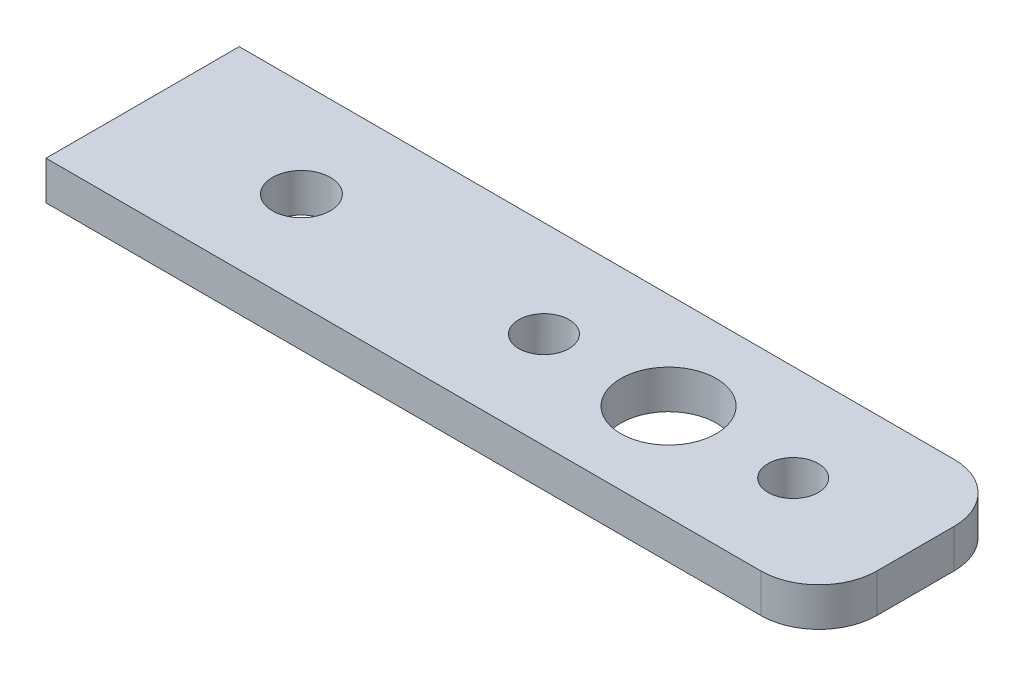
SolidWorks part; units mm, degrees
ref_plane "Front Plane" through (0, 0, 0) normal (0, 0, 1) x (1, 0, 0)
ref_plane "Top Plane" through (0, 0, 0) normal (0, 1, 0) x (1, 0, 0)
ref_plane "Right Plane" through (0, 0, 0) normal (1, 0, 0) x (0, 0, -1)
sketch "Sketch1" plane through (0, 0, 0) normal (0, 1, 0) x (1, 0, 0)
  line L1 (-20, 5) -> (20, 5)
  line L2 (-20, 5) -> (-20, -5)
  line L3 (-20, -5) -> (20, -5)
  line L4 (20, 5) -> (20, -5)
  line L5 (-20, 5) -> (20, -5) construction
  line L6 (-20, -5) -> (20, 5) construction
  point P0 (0, 0)
  dimension "D1" = 10
  dimension "D2" = 40
extrude "Boss-Extrude1" add sketch "Sketch1" along normal blind 2
sketch "Sketch2" plane through (0, 2, 0) normal (0, 1, 0) x (1, 0, 0)
  line L0 (7.2199, 5) -> (7.2199, -5) construction
  line L1 (-20, -5) -> (20, -5) construction
  circle A0 centre (7.2199, 0) radius 2.4729
  circle A1 centre (13.6699, 0) radius 1.3
  circle A3 centre (0.7699, 0) radius 1.3
  point P10 (7.2199, 0)
  point P11 (7.2199, 0)
  dimension "D1" = 2.6
  dimension "D2" = 6.45
extrude "Cut-Extrude1" cut sketch "Sketch2" against normal blind 3
fillet "Fillet1" radius 3 2 edges at (20, 1, 5) (20, 1, -5)
hole_wizard "Ø3.0 (3) Diameter Hole1" positions "Sketch3" profile "Sketch4" hole size "Ø3.0" standard "BSI" end condition through all
sketch "Sketch3" plane through (0, 2, 0) normal (0, 1, 0) x (1, 0, 0)
  point P0 (-11.7813, 0)
  point P3 (-6.9218, 0)
  point P4 (-11.7813, 0)
sketch "Sketch4" plane through (-11.7813, 2, 0) normal (1, 0, 0) x (0, 0, 1)
  line L0 (0, 0) -> (0, 2)
  line L1 (0, 2) -> (1.5, 2)
  line L2 (1.5, 2) -> (1.5, 0)
  line L5 (1.5, 0) -> (0, 0)
  line L11 (0, -6.35) -> (0, 107.95) construction
  dimension "Thru Hole Dia." = 3
  dimension "Thru Hole Depth" = 2
